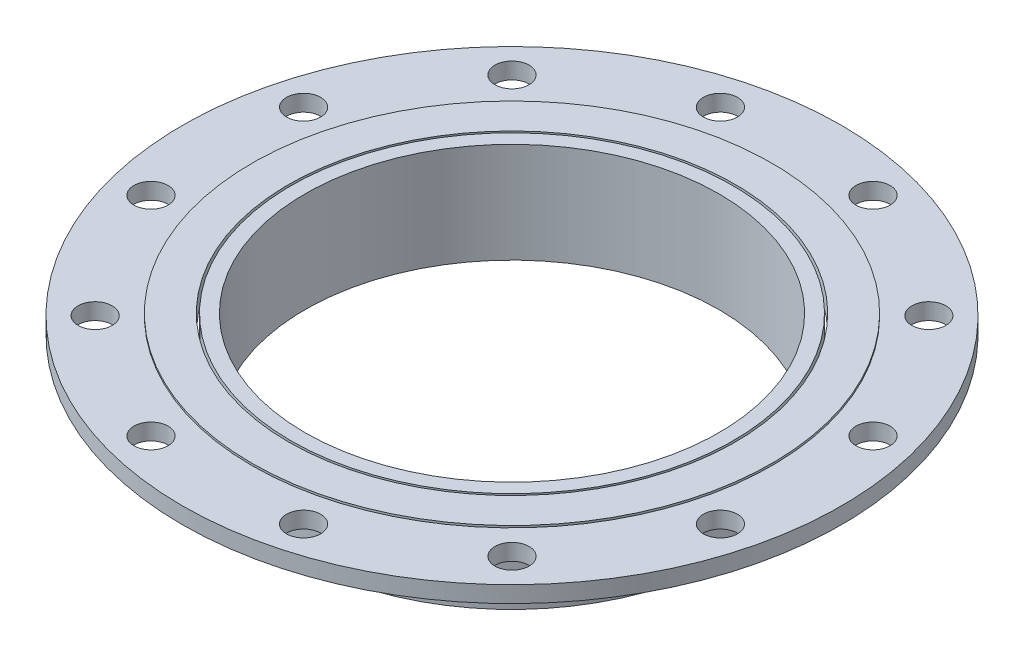
SolidWorks part; units mm, degrees
ref_plane "Front Plane" through (0, 0, 0) normal (0, 0, 1) x (1, 0, 0)
ref_plane "Top Plane" through (0, 0, 0) normal (0, 1, 0) x (1, 0, 0)
ref_plane "Right Plane" through (0, 0, 0) normal (1, 0, 0) x (0, 0, -1)
ref_plane "Plane1" through (0, 350, 0) normal (0, 1, 0) x (1, 0, 0)
ref_plane "Plane2" through (0, 400, 0) normal (0, 1, 0) x (1, 0, 0)
sketch "Sketch9" plane through (0, 400, 0) normal (0, 1, 0) x (1, 0, 0)
  circle A0 centre (0, 0) radius 241.5
  circle A1 centre (0, 0) radius 163.6
  dimension "D1" = 483
  dimension "D2" = 327.2
extrude "Boss-Extrude1" add sketch "Sketch9" along normal blind 12 contours A1 | A0 region at (0, 400, 0)
sketch "Sketch10" plane through (0, 412, 0) normal (0, 1, 0) x (1, 0, 0)
  line L0 (0, 0) -> (0, 272.0092) construction
  line L1 (0, 0) -> (-55.9049, 208.64) construction
  circle A0 centre (0, 0) radius 216 construction
  circle A1 centre (-55.9049, 208.64) radius 12.5
  dimension "D2" = 432
  dimension "D3" = 25
  dimension "D1" = 15
extrude "Cut-Extrude1" cut sketch "Sketch10" against normal blind 12
ref_axis "Axis1" through (0, 456.0583, 0) along (0, -1, 0)
pattern_circular "CirPattern1" count 12 over 360 about axis through (0, 456.0583, 0) along (0, -1, 0) of "Cut-Extrude1"
sketch "Sketch11" plane through (0, 412, 0) normal (0, 1, 0) x (1, 0, 0)
  circle A0 centre (0, 0) radius 163.6
  circle A1 centre (0, 0) radius 190.5
  dimension "D1" = 381
extrude "Boss-Extrude2" add sketch "Sketch11" along normal blind 1.5
sketch "Sketch12" plane through (0, 413.5, 0) normal (0, 1, 0) x (1, 0, 0)
  circle A0 centre (0, 0) radius 161.95
  circle A1 centre (0, 0) radius 151.64
  dimension "D1" = 323.9
  dimension "D2" = 10.31
extrude "Boss-Extrude3" add sketch "Sketch12" against normal blind 73.5 separate body
